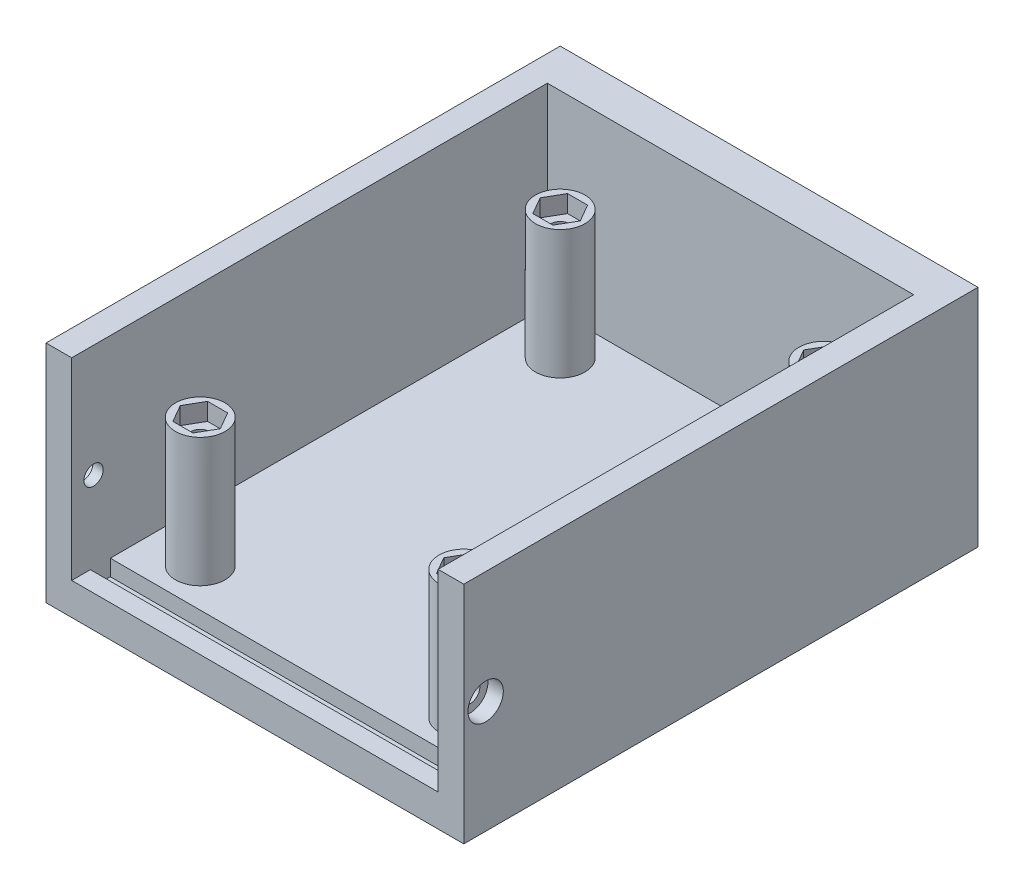
SolidWorks part; units mm, degrees
ref_plane "Front Plane" through (0, 0, 0) normal (0, 0, 1) x (1, 0, 0)
ref_plane "Top Plane" through (0, 0, 0) normal (0, 1, 0) x (1, 0, 0)
ref_plane "Right Plane" through (0, 0, 0) normal (1, 0, 0) x (0, 0, -1)
sketch "Sketch1" plane through (0, 0, 0) normal (0, 1, 0) x (1, 0, 0)
  line L0 (-32.5, 40) -> (32.5, -40) construction
  line L1 (-32.5, -40) -> (32.5, -40)
  line L2 (-32.5, -40) -> (-32.5, 40)
  line L3 (-32.5, 40) -> (32.5, 40)
  line L4 (32.5, -40) -> (32.5, 40)
  line L5 (32.5, 40) -> (-32.5, -40) construction
  point P4 (0, 0)
  dimension "D1" = 65
  dimension "D2" = 80
extrude "Boss-Extrude1" add sketch "Sketch1" along normal blind 5
sketch "Sketch2" plane through (0, 5, 0) normal (0, 1, 0) x (1, 0, 0)
  line L0 (-28.5, 34) -> (28.5, -34) construction
  line L1 (-28.5, -34) -> (28.5, -34)
  line L2 (-28.5, -34) -> (-28.5, 34)
  line L3 (-28.5, 34) -> (28.5, 34)
  line L4 (28.5, -34) -> (28.5, 34)
  line L5 (28.5, 34) -> (-28.5, -34) construction
  line L7 (-32.5, -40) -> (32.5, -40)
  line L8 (-32.5, -40) -> (-32.5, 40)
  line L9 (-32.5, 40) -> (32.5, 40)
  line L10 (32.5, -40) -> (32.5, 40)
  point P4 (0, 0)
  dimension "D1" = 68
  dimension "D2" = 57
extrude "Boss-Extrude2" add sketch "Sketch2" along normal blind 30
sketch "Sketch3" plane through (0, 5, 0) normal (0, 1, 0) x (1, 0, 0)
  line L6 (-20.5, 28) -> (20.5, 28) construction
  line L7 (-20.5, 28) -> (-20.5, -28) construction
  line L8 (-20.5, -28) -> (20.5, -28) construction
  line L9 (20.5, 28) -> (20.5, -28) construction
  line L10 (-20.5, 28) -> (20.5, -28) construction
  line L11 (-20.5, -28) -> (20.5, 28) construction
  circle A0 centre (-20.5, -28) radius 3.85
  circle A1 centre (20.5, -28) radius 3.85
  circle A2 centre (20.5, 28) radius 3.85
  circle A3 centre (-20.5, 28) radius 3.85
  point P0 (0, 0)
  point P1 (0, 0)
  point P4 (0, 0)
  dimension "D5" = 7.7
  dimension "D8" = 7.7
  dimension "D13" = 7.7
  dimension "D16" = 7.7
  dimension "D2" = 56
  dimension "D3" = 41
extrude "Boss-Extrude3" add sketch "Sketch3" along normal blind 20
hole_wizard "Ø3.0mm Dowel Hole1" positions "Sketch10" profile "Sketch5" hole size "Ø3.0" standard "ISO"
sketch "Sketch10" plane through (0, 25, 0) normal (0, 1, 0) x (1, 0, 0)
  point P0 (-20.5, 28)
  point P3 (20.5, 28)
  point P6 (20.5, -28)
  point P9 (-20.5, -28)
sketch "Sketch5" plane through (-20.5, 25, -28) normal (1, 0, 0) x (0, 0, 1)
  line L0 (0, 0) -> (0, 9.4013)
  line L1 (0, 9.4013) -> (1.5, 8.5)
  line L2 (1.5, 8.5) -> (1.5, 0.025)
  line L3 (1.5, 0.025) -> (1.525, 0)
  line L5 (1.525, 0) -> (0, 0)
  line L6 (-1.5, 0.025) -> (-1.525, 0) construction
  line L10 (0, 9.4013) -> (-1.5, 8.5) construction
  line L11 (0, -6.35) -> (0, 107.95) construction
  dimension "Hole Dia." = 3
  dimension "Hole Depth" = 8.5
  dimension "Near C'Sink Dia." = 3.05
  dimension "Near C'Sink Angle" = 90
  dimension "Drill Angle" = 118
sketch "Sketch8" plane through (0, 25, 0) normal (0, 1, 0) x (1, 0, 0)
  line L1 (-17.3823, 28) -> (-18.9412, 30.7)
  line L2 (-18.9412, 30.7) -> (-22.0588, 30.7)
  line L3 (-22.0588, 30.7) -> (-23.6177, 28)
  line L4 (-23.6177, 28) -> (-22.0588, 25.3)
  line L5 (-22.0588, 25.3) -> (-18.9412, 25.3)
  line L6 (-18.9412, 25.3) -> (-17.3823, 28)
  circle A0 centre (-20.5, 28) radius 2.7 construction
  circle A1 centre (-20.5, 28) radius 1.525 construction
  dimension "D1" = 2.7
  dimension "D2" = 3.1177
extrude "Cut-Extrude1" cut sketch "Sketch8" against normal blind 2.7
mirror "Mirror1" about plane through (0, 0, 0) normal (0, 0, 1) of "Cut-Extrude1" second plane through (0, 0, 0) second plane normal (1, 0, 0)
sketch "Sketch13" plane through (32.5, 0, 0) normal (1, 0, 0) x (0, 0, -1)
  line L0 (-40, 17.5) -> (40, 17.5) construction
  line L1 (-40, 35) -> (-40, 0) construction
  line L2 (40, 35) -> (40, 0) construction
  circle A1 centre (-36.6, 17.5) radius 2.75
  dimension "D1" = 5.5
  dimension "D3" = 3.4
extrude "Cut-Extrude4" cut sketch "Sketch13" against normal blind 2.4
sketch "Sketch14" plane through (32.5, 0, 0) normal (1, 0, 0) x (0, 0, -1)
  circle A0 centre (-36.6, 17.5) radius 1.5
extrude "Cut-Extrude5" cut sketch "Sketch14" against normal blind 4
mirror "Mirror2" about plane through (0, 0, 0) normal (1, 0, 0) of "Cut-Extrude5", "Cut-Extrude4"
sketch "Sketch11" plane through (0, 35, 0) normal (0, 1, 0) x (1, 0, 0)
  line L0 (-32.5, -40) -> (32.5, -40) construction
  line L1 (-28.5, -34) -> (28.5, -34)
  line L2 (-28.5, -34) -> (-28.5, -40)
  line L3 (-28.5, -40) -> (28.5, -40)
  line L4 (28.5, -34) -> (28.5, -40)
  line L5 (-28.5, -34) -> (28.5, -40) construction
  line L6 (-28.5, -40) -> (28.5, -34) construction
  line L7 (28.5, -34) -> (28.5, 34) construction
  point P4 (0, -37)
  dimension "D1" = 6
extrude "Cut-Extrude2" cut sketch "Sketch11" against normal blind 30
sketch "Sketch15" plane through (0, 5, 0) normal (0, 1, 0) x (1, 0, 0)
  line L0 (-28.5, 34) -> (-28.5, -40) construction
  line L1 (-28.5, -34) -> (28.5, -34)
  line L2 (-28.5, -34) -> (-28.5, -37.1)
  line L3 (-28.5, -37.1) -> (28.5, -37.1)
  line L4 (28.5, -34) -> (28.5, -37.1)
  line L5 (-28.5, -34) -> (28.5, -37.1) construction
  line L6 (-28.5, -37.1) -> (28.5, -34) construction
  line L7 (28.5, -40) -> (28.5, 34) construction
  line L8 (-28.5, -40) -> (28.5, -40) construction
  point P4 (0, -35.55)
  dimension "D1" = 2.9
  dimension "D2" = 3.1
extrude "Cut-Extrude6" cut sketch "Sketch15" against normal blind 2.5
